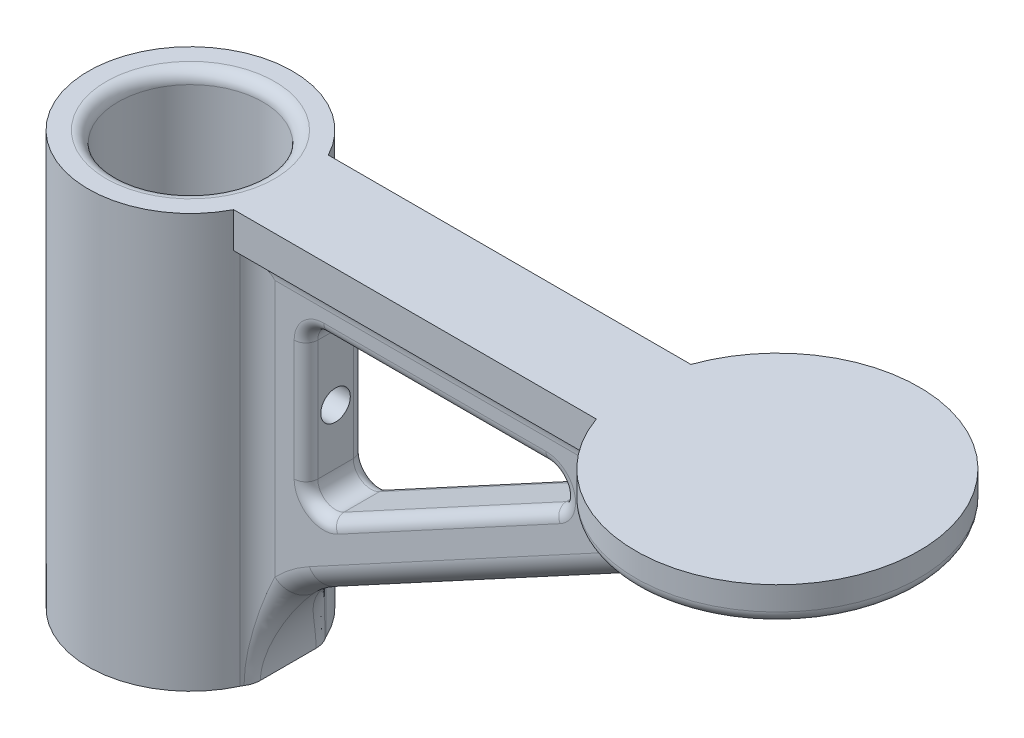
SolidWorks part; units mm, degrees
material "ABS"
ref_plane "前视基准面" through (0, 0, 0) normal (0, 0, 1) x (1, 0, 0)
ref_plane "上视基准面" through (0, 0, 0) normal (0, 1, 0) x (1, 0, 0)
ref_plane "右视基准面" through (0, 0, 0) normal (1, 0, 0) x (0, 0, -1)
sketch "草图1" plane through (0, 0, 0) normal (0, 1, 0) x (1, 0, 0)
  circle A0 centre (0, 0) radius 6.125
  circle A1 centre (0, 0) radius 8.625
  dimension "D1" = 12.25
  dimension "D2" = 2.5
extrude "凸台-拉伸1" add sketch "草图1" along normal blind 35
sketch "草图2" plane through (0, 35, 0) normal (0, 1, 0) x (1, 0, 0)
  line L0 (28.6414, 0) -> (0, 0) construction
  line L1 (49.6414, 4) -> (7.6414, 4)
  line L2 (49.6414, 4) -> (49.6414, -4)
  line L3 (49.6414, -4) -> (7.6414, -4)
  line L4 (7.6414, 4) -> (7.6414, -4)
  line L5 (49.6414, 4) -> (7.6414, -4) construction
  line L6 (49.6414, -4) -> (7.6414, 4) construction
  circle A0 centre (0, 0) radius 8.625 construction
  point P0 (28.6414, 0)
  point P5 (7.1911, 4.7622)
  point P11 (17.9252, 0)
  dimension "D1" = 42
  dimension "D2" = 8
extrude "凸台-拉伸2" add sketch "草图2" against normal blind 3
sketch "草图3" plane through (0, 35, 0) normal (0, 1, 0) x (1, 0, 0)
  line L0 (49.6414, -4) -> (49.6414, 4) construction
  circle A0 centre (49.6414, 0) radius 12
extrude "凸台-拉伸3" add sketch "草图3" against normal up to surface (3 mm away) up to face at (28.8873, 32, 0)
sketch "草图4" plane through (0, 0, 0) normal (0, 0, 1) x (1, 0, 0)
  line L0 (12.2714, 26.5) -> (12.2714, 16.3258)
  line L1 (14.4852, 15.0066) -> (33.2868, 25.1808)
  line L2 (13.5121, 8.7949) -> (54.1674, 30.7949)
  line L3 (38.3277, 32) -> (61.6414, 32) construction
  line L5 (58.9266, 32) -> (58.9266, 33.4504)
  line L6 (58.9266, 33.4504) -> (11.2893, 33.4504)
  line L7 (32.5729, 28) -> (13.7714, 28)
  line L8 (7.6414, 32) -> (38.3277, 32) construction
  line L10 (-8.625, 0) -> (8.625, 0) construction
  line L11 (8.2714, 0) -> (8.2714, 35)
  line L12 (7.6414, 35) -> (38.3277, 35) construction
  line L13 (8.2714, 35) -> (11.2893, 33.4504)
  arc A0 (54.1674, 30.7949) -> (58.9266, 32) centre (58.9266, 22) cw
  arc A1 (8.2714, 0) -> (13.5121, 8.7949) centre (18.2714, 0) cw
  arc A2 (33.2868, 25.1808) -> (32.5729, 28) centre (32.5729, 26.5) ccw
  arc A3 (14.4852, 15.0066) -> (12.2714, 16.3258) centre (13.7714, 16.3258) cw
  arc A4 (13.7714, 28) -> (12.2714, 26.5) centre (13.7714, 26.5) ccw
  point P17 (49.851, 32)
  point P26 (0, 0)
  point P27 (8.2909, 0)
  point P28 (8.2714, 0)
  point P31 (52.7683, 32)
  point P32 (53.5968, 32)
  dimension "D1" = 10
  dimension "D5" = 1.5
  dimension "D2" = 4
  dimension "D3" = 5
  dimension "D4" = 4
extrude "凸台-拉伸4" add sketch "草图4" along normal mid plane 5
sketch "草图5" plane through (0, 0, 0) normal (0, -1, 0) x (1, 0, 0)
  line L0 (16.1345, 2.5) -> (9.6426, 2.5)
  line L1 (16.1345, 2.5) -> (16.1345, -2.5)
  line L2 (16.1345, -2.5) -> (9.6426, -2.5)
  line L4 (8.2714, 2.5) -> (58.9266, 2.5) construction
  arc A0 (7.8302, 3.6542) -> (7.8302, -3.6542) centre (0, 0) ccw
  circle A2 centre (0, 0) radius 7.0403
  arc A5 (7.8302, -3.6542) -> (9.6426, -2.5) centre (9.6426, -4.5) cw
  arc A6 (9.6426, 2.5) -> (7.8302, 3.6542) centre (9.6426, 4.5) cw
  point P10 (8.2714, -2.5)
  point P13 (8.2714, 2.5)
  point P14 (8.2714, -2.5)
  point P15 (-0.0462, 0)
  point P19 (8.2714, 2.5)
  dimension "D1" = 2
extrude "凸台-拉伸5" add sketch "草图5" against normal through all
sketch "草图6" plane through (16.1345, 0, 0) normal (1, 0, 0) x (0, 0, -1)
  line L0 (-4, 35) -> (-4, 32) construction
  line L1 (-12, 32) -> (12, 32) construction
  line L3 (-2.5, 32) -> (-2.5, 0) construction
  line L4 (-2.5, 23.5695) -> (2.5, 23.5695)
  line L5 (-2.5, 23.5695) -> (-2.5, 30.0635)
  line L6 (-4, 32) -> (-4, 33.8908)
  line L7 (2.5, 23.5695) -> (2.5, 30.0635)
  line L8 (0, 23.5695) -> (0, 33.8908) construction
  line L9 (-4, 33.8908) -> (4, 33.8908)
  line L10 (4, 33.8908) -> (4, 32)
  line L11 (-2.5, 10.2139) -> (-2.5, 30.7949) construction
  arc A0 (-2.5, 30.0635) -> (-4, 32) centre (-4.5, 30.0635) ccw
  arc A1 (2.5, 30.0635) -> (4, 32) centre (4.5, 30.0635) cw
  point P15 (2.5, 32)
  point P18 (2.5, 29.9578)
  dimension "D1" = 2
extrude "凸台-拉伸6" add sketch "草图6" along normal blind 49 and the other way blind 9
sketch "草图7" plane through (0, 35, 0) normal (0, 1, 0) x (1, 0, 0)
  line L0 (49.6414, -12) -> (72.4449, -18.3508)
  line L1 (72.4449, -18.3508) -> (71.5327, 21.1752)
  line L2 (71.5327, 21.1752) -> (49.8986, 11.9972)
  arc A0 (49.6414, -12) -> (49.8986, 11.9972) centre (49.6414, 0) ccw
  arc A1 (38.3277, -4) -> (38.3277, 4) centre (49.6414, 0) ccw construction
  point P1 (49.898, 11.9684)
  point P9 (49.0278, -12)
extrude "切除-拉伸1" cut sketch "草图7" against normal through all both and the other way through all
sketch "草图8" plane through (0, 0, 2.5) normal (0, 0, 1) x (1, 0, 0)
  line L0 (13.5121, 8.7949) -> (54.1674, 30.7949)
  line L1 (8.2714, 0) -> (66.0076, -12.8335)
  line L2 (58.9266, 32) -> (63.736, 32)
  line L3 (63.736, 32) -> (66.0076, -12.8335)
  line L4 (14.4852, 15.0066) -> (33.2868, 25.1808)
  line L5 (32.5729, 28) -> (13.7714, 28)
  line L6 (12.2714, 26.5) -> (12.2714, 16.3258)
  arc A0 (58.9266, 32) -> (54.1674, 30.7949) centre (58.9266, 22) ccw
  arc A1 (13.5121, 8.7949) -> (8.2714, 0) centre (18.2714, 0) ccw
  arc A2 (33.2868, 25.1808) -> (32.5729, 28) centre (32.5729, 26.5) ccw
  arc A3 (13.7714, 28) -> (12.2714, 26.5) centre (13.7714, 26.5) ccw
  arc A4 (12.2714, 16.3258) -> (14.4852, 15.0066) centre (13.7714, 16.3258) ccw
  point P27 (63.736, 32)
extrude "切除-拉伸2" cut sketch "草图8" against normal through all both and the other way through all
hole_wizard "孔1" positions "草图10" profile "草图11" legacy end condition through all
sketch "草图10" plane through (12.2714, 0, 0) normal (1, 0, 0) x (0, 0, -1)
  line L0 (12, 35) -> (-12, 35) construction
  point P0 (0, 21)
  dimension "D1" = 14
sketch "草图11" plane through (12.2714, 21, 0) normal (0, 1, 0) x (0, 0, -1)
  line L0 (0, 0) -> (0, 20.9123)
  line L1 (0, 20.9123) -> (1.25, 20.9123)
  line L2 (1.25, 20.9123) -> (1.25, 0)
  line L3 (1.25, 0) -> (0, 0)
  line L4 (0, 110) -> (0, -10) construction
  dimension "直径" = 2.5
  dimension "深度" = 20.9123
fillet "圆角2" radius 1 1 edges at (13.0035, 15.0372, 2.5) type face fillet first side face at (19.8451, 23.1621, 2.5) second side face at (13.1909, 15.3517, 0)
fillet "圆角3" radius 1 1 edges at (12.2714, 21.4129, -2.5) type face fillet first side face at (19.8451, 23.1621, -2.5) second side face at (12.2714, 21, -1.25)
fillet "圆角6" radius 1 1 edges at (0, 35, 6.125) type face fillet first side face at (24.7469, 35, 0) second side face at (-6.0017, 20.7413, 1.2229)
fillet "圆角7" radius 1 1 edges at (0, 0, 6.125) type face fillet first side face at (0, 0, 6.125) second side face at (0, 34, 6.125)
fillet "圆角11" radius 2 1 edges at (33.164, 19.4292, 2.5) type face fillet first side face at (19.7162, 23.1978, 2.5) second side face at (40.1691, 23.2199, 0)
fillet "圆角12" radius 2 1 edges at (33.164, 19.4292, -2.5) type face fillet first side face at (19.7162, 23.1978, -2.5) second side face at (39.6481, 22.938, -0.9076)
fillet "圆角13" radius 1 1 edges at (61.6414, 32, 0) type face fillet first side face at (55.591, 32, 0) second side face at (49.9845, 33.5, 0)
